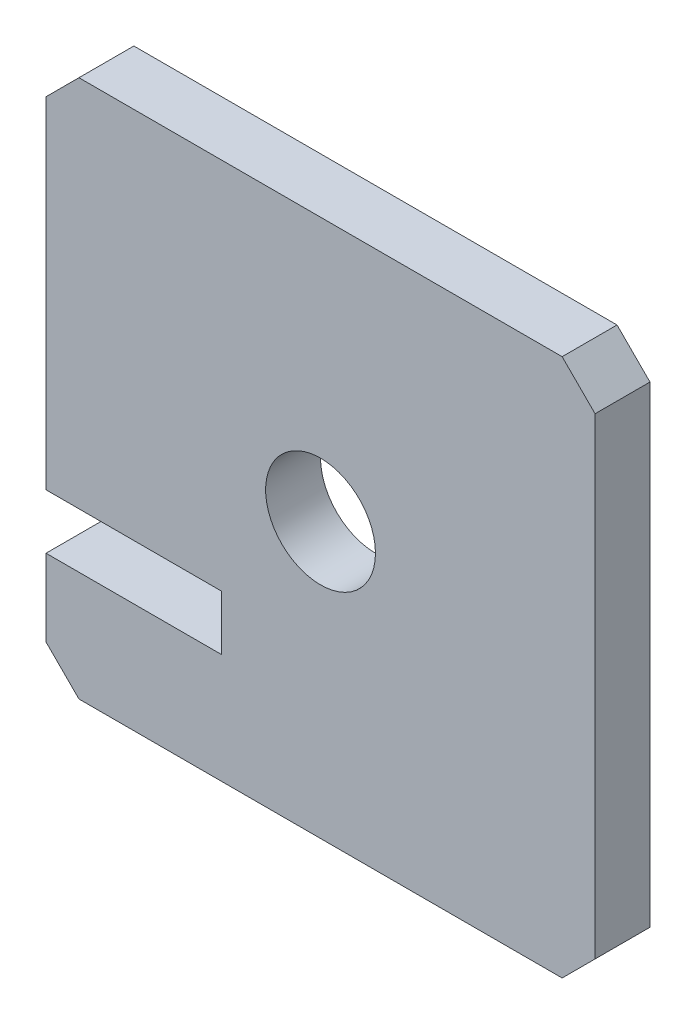
SolidWorks part; units mm, degrees
material "6061-T4 (SS)"
ref_plane "Front Plane" through (0, 0, 0) normal (0, 0, 1) x (1, 0, 0)
ref_plane "Top Plane" through (0, 0, 0) normal (0, 1, 0) x (1, 0, 0)
ref_plane "Right Plane" through (0, 0, 0) normal (1, 0, 0) x (0, 0, -1)
sketch "Sketch1" plane through (0, 0, 0) normal (0, 0, 1) x (1, 0, 0)
  line L0 (-22, 24) -> (22, 24)
  line L1 (22, 24) -> (25, 21)
  line L2 (25, 21) -> (25, -22)
  line L3 (25, -22) -> (22, -25)
  line L4 (22, -25) -> (-22, -25)
  line L5 (-22, -25) -> (-25, -22)
  line L6 (-25, -22) -> (-25, -15)
  line L7 (-25, 21) -> (-22, 24)
  line L8 (-25, -10) -> (-25, 21)
  line L9 (-25, -10) -> (-9, -10)
  line L11 (-25, -15) -> (-9, -15)
  line L12 (-9, -10) -> (-9, -15)
  circle A0 centre (0, 0) radius 5
  point P15 (0, 24)
  point P17 (0, -25)
  dimension "D1" = 10
  dimension "D2" = 24
  dimension "D3" = 7
  dimension "D4" = 16
  dimension "D5" = 43
  dimension "D6" = 44
  dimension "D7" = 50
  dimension "D8" = 31
  dimension "D9" = 45
extrude "Boss-Extrude1" add sketch "Sketch1" along normal blind 5
